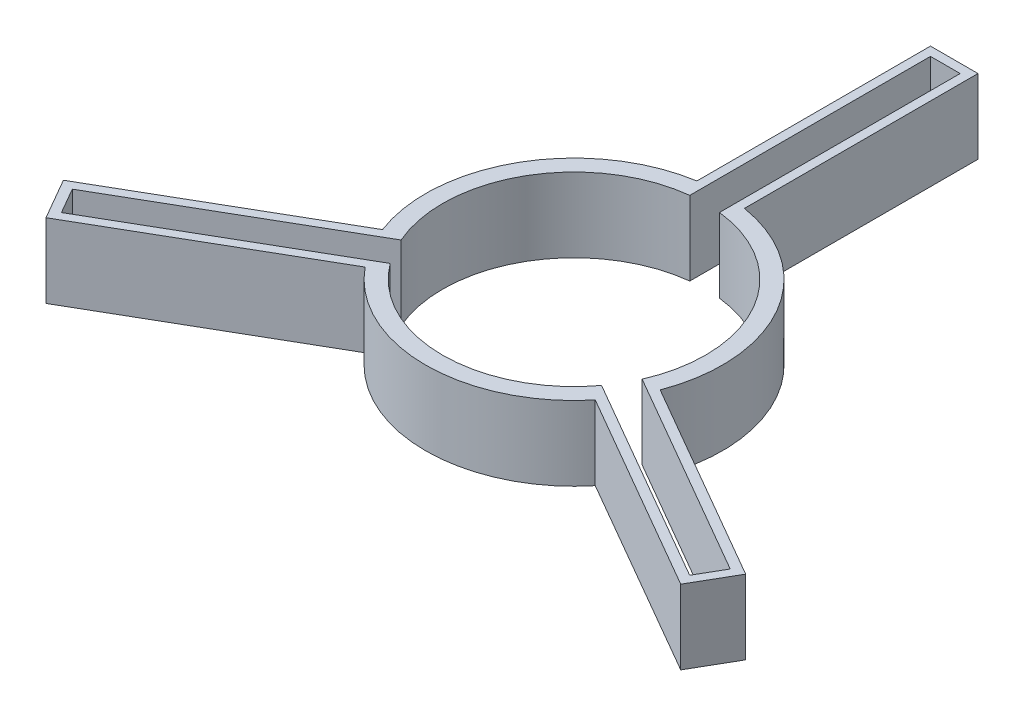
SolidWorks part; units mm, degrees
ref_plane "Front Plane" through (0, 0, 0) normal (0, 0, 1) x (1, 0, 0)
ref_plane "Top Plane" through (0, 0, 0) normal (0, 1, 0) x (1, 0, 0)
ref_plane "Right Plane" through (0, 0, 0) normal (1, 0, 0) x (0, 0, -1)
sketch "Sketch1" plane through (0, 0, 0) normal (0, 1, 0) x (1, 0, 0)
  line L0 (0, 31.7123) -> (0, -45.2268) construction
  line L1 (-53.2552, 0) -> (46.6987, 0) construction
  line L2 (0, 0) -> (-38.2602, -22.0895) construction
  line L3 (0, 0) -> (33.0071, -19.0567) construction
  line L4 (-2, 17.5866) -> (-2, 50)
  line L5 (-2, 50) -> (2, 50)
  line L6 (2, 50) -> (2, 17.5866)
  line L7 (-3.2, 51.2) -> (-3.2, 19.7423)
  line L8 (-3.2, 51.2) -> (3.2, 51.2)
  line L9 (3.2, 51.2) -> (3.2, 19.7423)
  line L10 (16.2305, -7.0613) -> (44.3013, -23.2679)
  line L11 (44.3013, -23.2679) -> (42.3013, -26.7321)
  line L12 (42.3013, -26.7321) -> (14.2305, -10.5254)
  line L13 (45.9405, -22.8287) -> (18.6974, -7.0999)
  line L14 (45.9405, -22.8287) -> (42.7405, -28.3713)
  line L15 (42.7405, -28.3713) -> (15.4974, -12.6425)
  line L16 (27.4636, -15.8561) -> (-39.1675, 22.6134) construction
  line L17 (-14.2305, -10.5254) -> (-42.3013, -26.7321)
  line L18 (-42.3013, -26.7321) -> (-44.3013, -23.2679)
  line L19 (-44.3013, -23.2679) -> (-16.2305, -7.0613)
  line L20 (-42.7405, -28.3713) -> (-15.4974, -12.6425)
  line L21 (-42.7405, -28.3713) -> (-45.9405, -22.8287)
  line L22 (-45.9405, -22.8287) -> (-18.6974, -7.0999)
  line L23 (-27.4636, -15.8561) -> (39.1675, 22.6134) construction
  circle A0 centre (0, 0) radius 17.7
  circle A1 centre (0, 0) radius 20
  point P16 (0, 51.2)
  point P19 (0, 20)
  point P43 (0, 0)
  dimension "D1" = 35.4
  dimension "D2" = 40
  dimension "D3" = 120
  dimension "D4" = 120
  dimension "D5" = 2
  dimension "D6" = 4
  dimension "D7" = 1.2
  dimension "D8" = 1.2
  dimension "D9" = 1.2
  dimension "D10" = 30
  dimension "D11" = 3
extrude "Boss-Extrude1" add sketch "Sketch1" along normal blind 10 contours A1 L22 L21 L20 L17 L18 L19 | A1 L12 A0 L17 | A1 L10 L11 L12 L15 L14 L13 | L10 A1 L6 A0 | A1 L9 L8 L7 L4 L5 L6 | L4 A1 L19 A0 region at (-15.6178, 0, -9.0169) region at (-2.6429, 0, -20.1484) region at (2.3339, 0, -18.7432) region at (-31.4532, 0, 15.4213) region at (0, 0, 18.0382) region at (18.817, 0, 7.8046)
